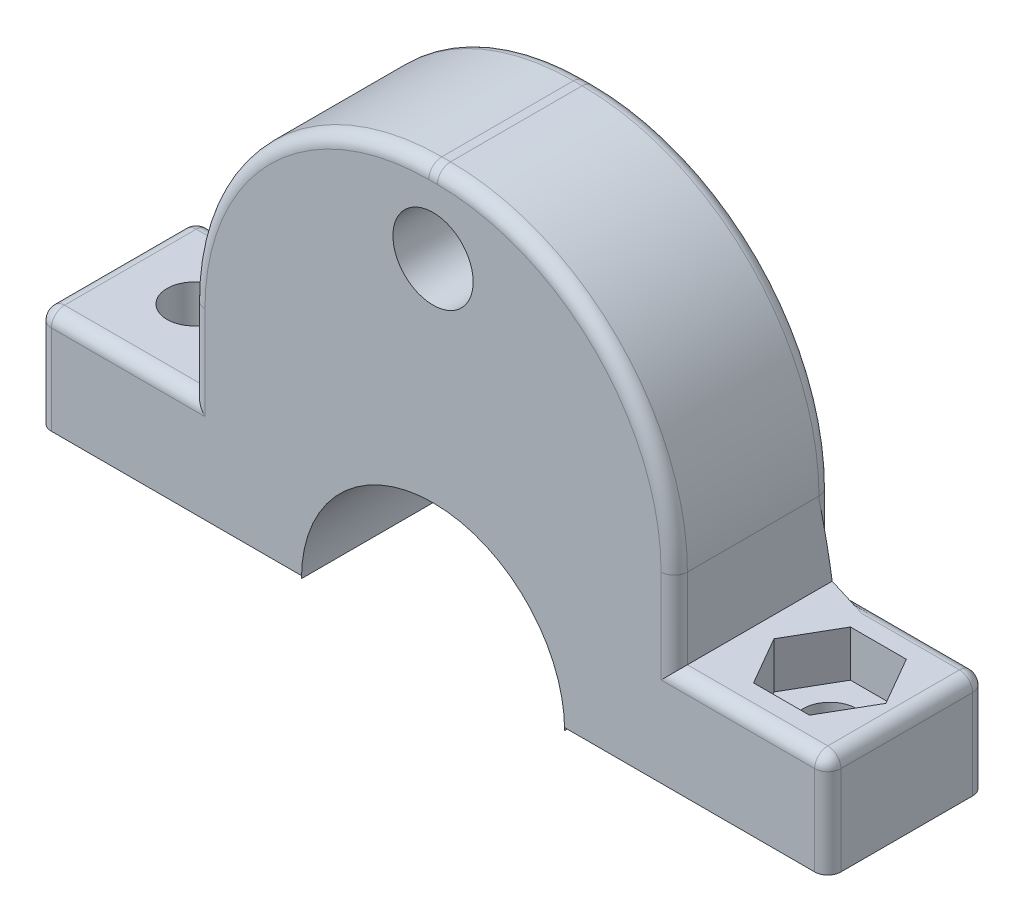
SolidWorks part; units mm, degrees
material "PLA"
ref_plane "Plan de face" through (0, 0, 0) normal (0, 0, 1) x (1, 0, 0)
ref_plane "Plan de dessus" through (0, 0, 0) normal (0, 1, 0) x (1, 0, 0)
ref_plane "Plan de droite" through (0, 0, 0) normal (1, 0, 0) x (0, 0, -1)
sketch "Esquisse1" plane through (0, 0, 0) normal (0, 0, 1) x (1, 0, 0)
  line L0 (-20, 0) -> (-10, 0)
  line L1 (10, 0) -> (20, 0)
  arc A1 (-10, 0) -> (10, 0) centre (0, 0) cw
  arc A2 (-20, 0) -> (20, 0) centre (0, 0) cw
  dimension "D1" = 10
  dimension "D2" = 10
extrude "Boss.-Extru.1" add sketch "Esquisse1" along normal blind 12
sketch "Esquisse2" plane through (0, 0, 0) normal (0, -1, 0) x (1, 0, 0)
  line L2 (20, 12) -> (30, 12)
  line L3 (30, 12) -> (30, 0)
  line L4 (30, 0) -> (20, 0)
  line L5 (0, 0) -> (0, 5.427) construction
  line L6 (-30, 12) -> (-30, 0)
  line L7 (-20, 12) -> (-30, 12)
  line L8 (-20, 12) -> (-20, 0)
  line L9 (-30, 0) -> (-20, 0)
  line L10 (-20, 0) -> (-10, 0) construction
  line L11 (-10, 12) -> (-10, 0) construction
  line L12 (-20, 12) -> (-10, 12) construction
  line L13 (10, 0) -> (20, 0) construction
  line L14 (10, 12) -> (10, 0) construction
  line L15 (10, 12) -> (20, 12) construction
  line L16 (-20, 0) -> (-10, 0)
  line L17 (-10, 12) -> (-10, 0)
  line L18 (-20, 12) -> (-10, 12)
  line L19 (10, 0) -> (20, 0)
  line L20 (10, 12) -> (10, 0)
  line L21 (10, 12) -> (20, 12)
  line L22 (20, 12) -> (20, 0) construction
  line L23 (20, 12) -> (20, 0)
  line L24 (25, 12) -> (25, 0) construction
  circle A0 centre (24.165, 7.5) radius 2.05
  circle A1 centre (-24.165, 7.5) radius 2.05
  dimension "D2" = 4.1
  dimension "D1" = 10
  dimension "D3" = 5.835
  dimension "D4" = 7.5
extrude "Boss.-Extru.2" [suppressed] add sketch "Esquisse2" against normal blind 8
sketch "Esquisse3" [suppressed] plane through (0, 8, 0) normal (0, 1, 0) x (1, 0, 0)
  line L0 (30, 0) -> (18.3303, 0) construction
  line L1 (26.29, -11.1806) -> (28.415, -7.5)
  line L2 (28.415, -7.5) -> (26.29, -3.8194)
  line L3 (26.29, -3.8194) -> (22.04, -3.8194)
  line L4 (22.04, -3.8194) -> (19.915, -7.5)
  line L5 (19.915, -7.5) -> (22.04, -11.1806)
  line L6 (22.04, -11.1806) -> (26.29, -11.1806)
  circle A0 centre (24.165, -7.5) radius 4.25 construction
  dimension "D1" = 8.5
extrude "Enlèv. mat.-Extru.1" [suppressed] cut sketch "Esquisse3" against normal blind 3.5
fillet "Congé1" [suppressed] radius 1
sketch "Esquisse4" [suppressed] plane through (0, 0, 15) normal (0, 0, 1) x (1, 0, 0)
  line L0 (0, 24) -> (0, 27.05) construction
  line L1 (0, 27.05) -> (0, 30.05) construction
  line L4 (18.3303, 8) -> (14.4151, 18.3707) construction
  line L5 (-18.3303, 8) -> (-14.4151, 18.3707) construction
  line L6 (-14.4151, 18.3707) -> (-2.5279, 28.0644) construction
  line L7 (14.4151, 18.3707) -> (2.5279, 28.0644) construction
  line L8 (-18.3303, 8) -> (-30, 8) construction
  circle A0 centre (0, 24) radius 3.05
  arc A1 (18.3303, 8) -> (-18.3303, 8) centre (0, 0) ccw construction
  arc A2 (18.3303, 8) -> (-18.3303, 8) centre (0, 0) ccw
  arc A3 (2.5279, 28.0644) -> (-2.5279, 28.0644) centre (0, 24.9644) ccw
  spline S1 degree 2 poles (-18.3303, 8) (-14.4151, 18.3707) (-2.5279, 28.0644) knots 0 0 0 1 1 1
  spline S2 degree 2 poles (18.3303, 8) (14.4151, 18.3707) (2.5279, 28.0644) knots 0 0 0 1 1 1
  dimension "D1" = 6.1
  dimension "D3" = 4
  dimension "D4" = 25.8334
  dimension "D6" = 2.5279
  dimension "D2" = 24
  dimension "D5" = 10.3707
extrude "Boss.-Extru.3" [suppressed] add sketch "Esquisse4" against normal up to surface (15 mm away)
sketch "Esquisse6" plane through (0, 0, 0) normal (0, 0, -1) x (-1, 0, 0)
  line L2 (10, 0) -> (20, 0)
  line L3 (-20, 0) -> (-10, 0)
  line L4 (10, 0) -> (20, 0)
  line L5 (-20, 0) -> (-10, 0)
  arc A2 (10, 0) -> (-10, 0) centre (0, 0) ccw
  arc A3 (20, 0) -> (-20, 0) centre (0, 0) ccw
  arc A4 (10, 0) -> (-10, 0) centre (0, 0) ccw
  arc A5 (20, 0) -> (-20, 0) centre (0, 0) ccw
  dimension "D1" = 0
ref_plane "Plan1" through (0, 0, -3) normal (0, 0, -1) x (-1, 0, 0)
sketch "Esquisse8" plane through (0, 0, -3) normal (0, 0, -1) x (-1, 0, 0)
  line L0 (-20, 0) -> (-10, 0) construction
  line L1 (10, 0) -> (11, 0)
  line L2 (-11, 0) -> (-10, 0)
  arc A0 (-10, 0) -> (10, 0) centre (0, 0) cw
  arc A1 (10, 0) -> (-10, 0) centre (0, 0) ccw construction
  arc A2 (-11, 0) -> (11, 0) centre (0, 0) cw
  dimension "D1" = 11
loft "Lissage1" add profiles "Esquisse6", "Esquisse8" connector at (20, 0, 0) connector at (11, 0, -3)
sketch "Esquisse9" plane through (0, 0, 0) normal (0, -1, 0) x (1, 0, 0)
  line L0 (20, 0) -> (10, 0)
  line L1 (10, 12) -> (10, -3) construction
  line L2 (0, 0) -> (0, 4.3678) construction
  line L3 (20, 12) -> (30, 12)
  line L5 (20, 0) -> (30, 0)
  line L6 (30, 12) -> (30, 0)
  line L7 (10, 12) -> (10, -3)
  line L8 (10, -3) -> (11, -3)
  line L9 (11, -3) -> (20, 0)
  line L10 (20, 0) -> (20, 12)
  line L11 (20, 12) -> (10, 12)
  line L12 (10, 12) -> (10, 0)
  line L16 (20, 12) -> (10, 12)
  line L17 (-20, 0) -> (-10, 0)
  line L18 (-10, 12) -> (-10, 0)
  line L19 (-20, 12) -> (-10, 12)
  line L20 (20, 12) -> (20, 0) construction
  line L21 (-20, 0) -> (-30, 0)
  line L22 (-30, 12) -> (-30, 0)
  line L23 (-20, 12) -> (-30, 12)
  circle A0 centre (24.16, 6) radius 2.05
  circle A1 centre (-24.16, 6) radius 2.05
  dimension "D3" = 4.1
  dimension "D2" = 10
  dimension "D4" = 6
  dimension "D5" = 5.84
  dimension "D1" = 0
extrude "Boss.-Extru.4" add sketch "Esquisse9" against normal blind 8
sketch "Esquisse10" plane through (0, 8, 0) normal (0, 1, 0) x (1, 0, 0)
  line L0 (18.3303, 0) -> (30, 0) construction
  line L1 (26.285, -9.6806) -> (28.41, -6)
  line L2 (28.41, -6) -> (26.285, -2.3194)
  line L3 (26.285, -2.3194) -> (22.035, -2.3194)
  line L4 (22.035, -2.3194) -> (19.91, -6)
  line L5 (19.91, -6) -> (22.035, -9.6806)
  line L6 (22.035, -9.6806) -> (26.285, -9.6806)
  circle A0 centre (24.16, -6) radius 4.25 construction
  dimension "D1" = 8.5
extrude "Enlèv. mat.-Extru.2" cut sketch "Esquisse10" against normal blind 3.5
fillet "Congé5" [suppressed] radius 1
sketch "Esquisse11" plane through (0, 0, 12) normal (0, 0, 1) x (1, 0, 0)
  line L0 (0, 26.0518) -> (0, 32.1023) construction
  line L1 (-18.3303, 8) -> (-18.3303, 14.1023)
  line L3 (-0.3303, 32.1023) -> (0.3303, 32.1023)
  line L4 (18.3303, 8) -> (18.3303, 14.1023)
  circle A0 centre (0, 26.0518) radius 3.05
  arc A1 (-18.3303, 14.1023) -> (-0.3303, 32.1023) centre (-0.3303, 14.1023) cw
  arc A2 (18.3303, 14.1023) -> (0.3303, 32.1023) centre (0.3303, 14.1023) ccw
  arc A8 (18.3303, 8) -> (-18.3303, 8) centre (0, 0) ccw
  point P10 (-18.3303, 32.1023)
  dimension "D1" = 6.1
  dimension "D6" = 20
  dimension "D2" = 26.0518
  dimension "D5" = 32.1023
extrude "Boss.-Extru.5" add sketch "Esquisse11" against normal up to vertex (12 mm away) up to point (18.3303, 8, 0)
fillet "Congé4" radius 1 20 edges at (18.3303, 11.0511, 0) (-18.3303, 11.0511, 0) (-13.0582, 26.8302, 0) (0, 32.1023, 0) (18.3303, 11.0511, 12) (-18.3303, 11.0511, 12) (-13.0582, 26.8302, 12) (0, 32.1023, 12) (-24.1652, 8, 12) (-30, 4, 12) (-30, 4, 0) (-30, 8, 6) (-24.1652, 8, 0) (30, 4, 12) (30, 4, 0) (30, 8, 6) (24.1652, 8, 0) (24.1652, 8, 12) (13.0582, 26.8302, 0) (13.0582, 26.8302, 12)
sketch "Esquisse13" plane through (0, 0, 0) normal (0, -1, 0) x (1, 0, 0)
  line L0 (30, 1) -> (30, 11) construction
  line L1 (29, 12) -> (10, 12) construction
  line L2 (10, 12) -> (10, -3) construction
  line L3 (10, -3) -> (11, -3) construction
  line L4 (11, -3) -> (20, 0) construction
  line L5 (20, 0) -> (29, 0) construction
  line L6 (-10, 12) -> (-29, 12) construction
  line L7 (-30, 11) -> (-30, 1) construction
  line L8 (-29, 0) -> (-20, 0) construction
  line L9 (-20, 0) -> (-11, -3) construction
  line L10 (-11, -3) -> (-10, -3) construction
  line L11 (-10, -3) -> (-10, 12) construction
  line L12 (30, 1) -> (30, 11)
  line L13 (29, 12) -> (10, 12)
  line L14 (10, 12) -> (10, -3)
  line L15 (10, -3) -> (11, -3)
  line L16 (11, -3) -> (20, 0)
  line L17 (20, 0) -> (29, 0)
  line L18 (-10, 12) -> (-29, 12)
  line L19 (-30, 11) -> (-30, 1)
  line L20 (-29, 0) -> (-20, 0)
  line L21 (-20, 0) -> (-11, -3)
  line L22 (-11, -3) -> (-10, -3)
  line L23 (-10, -3) -> (-10, 12)
  arc A0 (30, 11) -> (29, 12) centre (29, 11) ccw construction
  arc A1 (29, 0) -> (30, 1) centre (29, 1) ccw construction
  arc A2 (-29, 12) -> (-30, 11) centre (-29, 11) ccw construction
  arc A3 (-30, 1) -> (-29, 0) centre (-29, 1) ccw construction
  arc A4 (30, 11) -> (29, 12) centre (29, 11) ccw
  arc A5 (29, 0) -> (30, 1) centre (29, 1) ccw
  arc A6 (-29, 12) -> (-30, 11) centre (-29, 11) ccw
  arc A7 (-30, 1) -> (-29, 0) centre (-29, 1) ccw
sketch "Esquisse12" [suppressed] plane through (0, 0, 0) normal (0, -1, 0) x (1, 0, 0)
  line L1 (-30, 11) -> (-30, 1) construction
  line L2 (-29, 0) -> (-19.6932, 0) construction
  line L7 (-19.3162, -0.2279) -> (-11, -3) construction
  line L8 (-11, -3) -> (-10, -3) construction
  line L48 (-10, -3) -> (-10, 12) construction
  line L49 (-10, 12) -> (-29, 12) construction
  line L50 (19.6932, 0) -> (29, 0) construction
  line L51 (30, 1) -> (30, 11) construction
  line L52 (29, 12) -> (10, 12) construction
  line L53 (10, 12) -> (10, -3) construction
  line L54 (10, -3) -> (11, -3) construction
  line L55 (11, -3) -> (19.3162, -0.2279) construction
  line L56 (-30, 11) -> (-30, 1)
  line L57 (-29, 0) -> (-19.6932, 0)
  line L58 (-19.3162, -0.2279) -> (-11, -3)
  line L59 (-11, -3) -> (-10, -3)
  line L60 (-10, -3) -> (-10, 12)
  line L61 (-10, 12) -> (-29, 12)
  line L62 (19.6932, 0) -> (29, 0)
  line L63 (30, 1) -> (30, 11)
  line L64 (29, 12) -> (10, 12)
  line L65 (10, 12) -> (10, -3)
  line L66 (10, -3) -> (11, -3)
  line L67 (11, -3) -> (19.3162, -0.2279)
  arc A16 (-30, 1) -> (-29, 0) centre (-29, 1) ccw construction
  arc A17 (-19.6932, 0) -> (-19.3162, -0.2279) centre (-19, 0.7208) ccw construction
  arc A18 (-29, 12) -> (-30, 11) centre (-29, 11) ccw construction
  arc A19 (19.3162, -0.2279) -> (19.6932, 0) centre (19, 0.7208) ccw construction
  arc A20 (29, 0) -> (30, 1) centre (29, 1) ccw construction
  arc A21 (30, 11) -> (29, 12) centre (29, 11) ccw construction
  arc A22 (-30, 1) -> (-29, 0) centre (-29, 1) ccw
  arc A23 (-19.6932, 0) -> (-19.3162, -0.2279) centre (-19, 0.7208) ccw
  arc A24 (-29, 12) -> (-30, 11) centre (-29, 11) ccw
  arc A25 (19.3162, -0.2279) -> (19.6932, 0) centre (19, 0.7208) ccw
  arc A26 (29, 0) -> (30, 1) centre (29, 1) ccw
  arc A27 (30, 11) -> (29, 12) centre (29, 11) ccw
  circle A28 centre (24.16, 6) radius 2.05 construction
  circle A29 centre (-24.16, 6) radius 2.05 construction
  circle A30 centre (24.16, 6) radius 2.05
  circle A31 centre (-24.16, 6) radius 2.05
extrude "Enlèv. mat.-Extru.3" cut sketch "Esquisse13" against normal blind 0.2
extrude "Enlèv. mat.-Extru.4" [suppressed] cut sketch "Esquisse12" against normal blind 0.2
